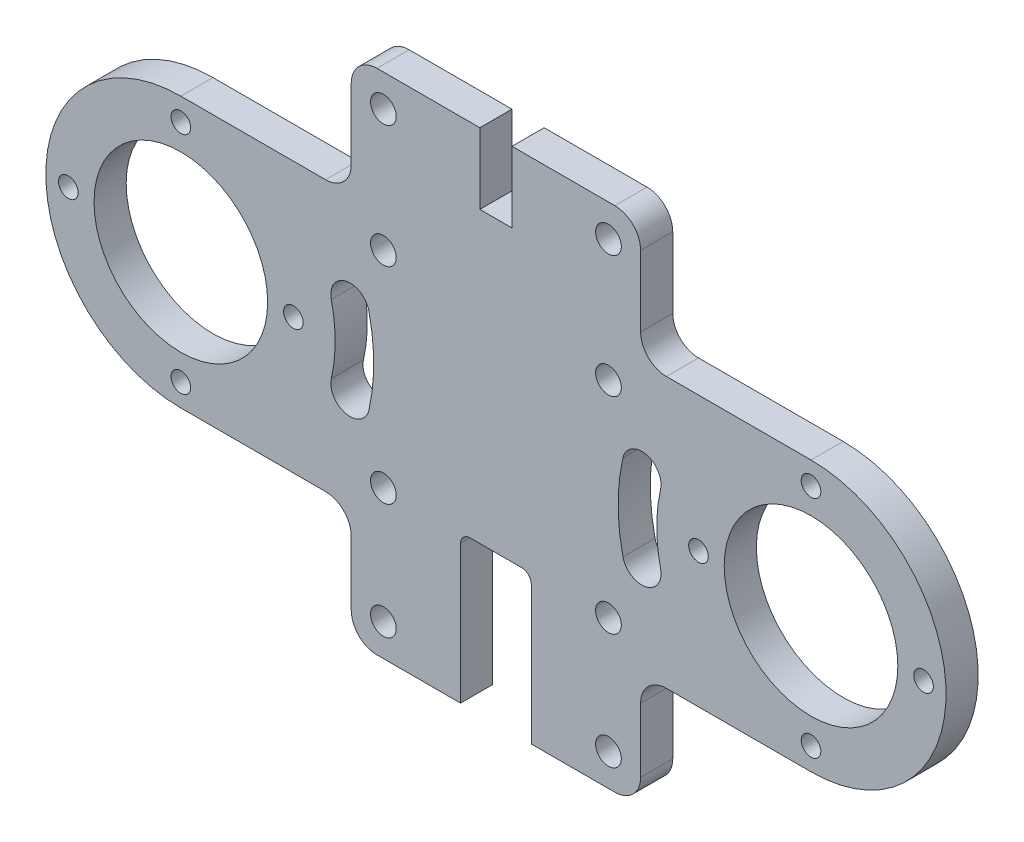
SolidWorks part; units mm, degrees
material "6061 Alloy"
ref_plane "Front Plane" through (0, 0, 0) normal (0, 0, 1) x (1, 0, 0)
ref_plane "Top Plane" through (0, 0, 0) normal (0, 1, 0) x (1, 0, 0)
ref_plane "Right Plane" through (0, 0, 0) normal (1, 0, 0) x (0, 0, -1)
sketch "Sketch1" plane through (0, 0, 0) normal (0, 0, 1) x (1, 0, 0)
  line L0 (-49, 26) -> (49, 26)
  line L1 (-49, -16) -> (49, -16)
  arc A1 (-49, 26) -> (-49, -16) centre (-49, 5) ccw
  arc A3 (49, -16) -> (49, 26) centre (49, 5) ccw
  arc A4 (49, -14) -> (49, -11) centre (49, -12.5) ccw construction
  arc A5 (66.5, 3.5) -> (66.5, 6.5) centre (66.5, 5) ccw construction
  arc A6 (31.5, 3.5) -> (31.5, 6.5) centre (31.5, 5) ccw construction
  arc A7 (49, 21) -> (49, 24) centre (49, 22.5) ccw construction
  arc A8 (-49, -14) -> (-49, -11) centre (-49, -12.5) ccw construction
  arc A9 (-31.5, 3.5) -> (-31.5, 6.5) centre (-31.5, 5) ccw construction
  arc A10 (-66.5, 3.5) -> (-66.5, 6.5) centre (-66.5, 5) ccw construction
  arc A11 (-49, 24) -> (-49, 21) centre (-49, 22.5) ccw construction
  circle A12 centre (49, -12.5) radius 1.5
  circle A13 centre (66.5, 5) radius 1.5
  circle A14 centre (31.5, 5) radius 1.5
  circle A15 centre (49, 22.5) radius 1.5
  circle A16 centre (-49, -12.5) radius 1.5
  circle A17 centre (-31.5, 5) radius 1.5
  circle A18 centre (-66.5, 5) radius 1.5
  circle A19 centre (-49, 22.5) radius 1.5
  arc A20 (-49, -8) -> (-49, 18) centre (-49, 5) ccw construction
  circle A21 centre (-49, 5) radius 13
  arc A22 (49, -8) -> (49, 18) centre (49, 5) ccw construction
  circle A23 centre (49, 5) radius 13
  dimension "D1" = 21
  dimension "D2" = 26
extrude "Boss-Extrude1" add sketch "Sketch1" along normal blind 5
sketch "Sketch2" plane through (0, 0, 0) normal (0, 0, -1) x (-1, 0, 0)
  circle A0 centre (-49, 5) radius 13.5
  circle A1 centre (49, 5) radius 13.5
  circle A2 centre (-49, 5) radius 13 construction
  dimension "D1" = 27
extrude "Cut-Extrude1" cut sketch "Sketch2" against normal blind 10
sketch "Sketch3" plane through (0, 0, 5) normal (0, 0, 1) x (1, 0, 0)
  line L0 (49, 26) -> (-49, 26) construction
  line L1 (0, 26) -> (0, -16) construction
  line L2 (-49, -16) -> (49, -16) construction
  line L3 (0, 5) -> (-11.8321, 5) construction
  circle A0 centre (49, 5) radius 24
  circle A1 centre (49, 5) radius 30
  arc A2 (19.7501, 11.6667) -> (25.6001, 10.3333) centre (22.6751, 11) cw
  arc A3 (19.7501, -1.6667) -> (25.6001, -0.3333) centre (22.6751, -1) ccw
  arc A4 (-19.7501, -1.6667) -> (-25.6001, -0.3333) centre (-22.6751, -1) cw
  arc A5 (-19.7501, 11.6667) -> (-25.6001, 10.3333) centre (-22.6751, 11) ccw
  circle A6 centre (-49, 5) radius 30
  circle A7 centre (-49, 5) radius 24
  dimension "D1" = 48
  dimension "D2" = 60
  dimension "D3" = 15
extrude "Cut-Extrude2" cut sketch "Sketch3" against normal blind 10 contours A5 A7 A4 A6 | A1 A3 A0 A2 region at (22.3515, 5, 5) region at (-22.3515, 5, 5)
sketch "Sketch4" plane through (0, 0, 0) normal (0, 0, -1) x (-1, 0, 0)
  line L0 (49, -16) -> (-49, -16) construction
  line L1 (5.5, -16) -> (-5.5, -16)
  line L2 (5.5, -16) -> (5.5, -11)
  line L3 (5.5, -11) -> (-5.5, -11)
  line L4 (-5.5, -16) -> (-5.5, -11)
  line L5 (0, 26) -> (0, -16) construction
  line L6 (-49, 26) -> (49, 26) construction
  dimension "D1" = 11
  dimension "D2" = 5
extrude "Cut-Extrude3" cut sketch "Sketch4" against normal blind 82
fillet "Fillet1" radius 1.5 2 edges at (-5.5, -11, 2.5) (5.5, -11, 2.5)
sketch "Sketch5" plane through (0, 0, 0) normal (0, 0, -1) x (-1, 0, 0)
  line L0 (0, 26) -> (0, -34) construction
  line L1 (-22.5, 45) -> (22.5, 45)
  line L2 (-22.5, 45) -> (-22.5, -34)
  line L3 (-22.5, -34) -> (22.5, -34)
  line L4 (22.5, 45) -> (22.5, -34)
  line L5 (-49, 26) -> (49, 26) construction
  line L6 (-5.5, -12.5) -> (-5.5, -16) construction
  line L7 (-2.5, 45) -> (2.5, 45)
  line L8 (-2.5, 45) -> (-2.5, 34)
  line L9 (-2.5, 34) -> (2.5, 34)
  line L10 (2.5, 45) -> (2.5, 34)
  line L11 (4, -11) -> (-4, -11) construction
  line L12 (5.5, -16) -> (5.5, -12.5) construction
  line L13 (-5.5, -12.5) -> (-5.5, -34)
  line L14 (4, -11) -> (-4, -11)
  line L15 (5.5, -34) -> (5.5, -12.5)
  line L17 (-17.5, 40) -> (17.5, 40) construction
  line L18 (-17.5, 40) -> (-17.5, -29) construction
  line L19 (-17.5, -29) -> (17.5, -29) construction
  line L20 (17.5, 40) -> (17.5, -29) construction
  arc A0 (-4, -11) -> (-5.5, -12.5) centre (-4, -12.5) ccw construction
  arc A1 (5.5, -12.5) -> (4, -11) centre (4, -12.5) ccw construction
  arc A2 (-4, -11) -> (-5.5, -12.5) centre (-4, -12.5) ccw
  arc A3 (5.5, -12.5) -> (4, -11) centre (4, -12.5) ccw
  circle A4 centre (-17.5, 40) radius 2
  circle A5 centre (17.5, 40) radius 2
  circle A6 centre (-17.5, -29) radius 2
  circle A7 centre (17.5, -29) radius 2
  arc M13 (19.7501, -1.6667) -> (19.7501, 11.6667) centre (49, 5) cw
  arc M14 (19.7501, 11.6667) -> (25.6001, 10.3333) centre (22.6751, 11) cw
  arc M16 (25.6001, -0.3333) -> (19.7501, -1.6667) centre (22.6751, -1) cw
  arc M17 (-25.6001, 10.3333) -> (-19.7501, 11.6667) centre (-22.6751, 11) cw
  arc M18 (-19.7501, 11.6667) -> (-19.7501, -1.6667) centre (-49, 5) cw
  arc M19 (-19.7501, -1.6667) -> (-25.6001, -0.3333) centre (-22.6751, -1) cw
  line M23 (-4, -11) -> (4, -11)
  arc M24 (4, -11) -> (5.5, -12.5) centre (4, -12.5) cw
  line M25 (5.5, -12.5) -> (5.5, -16)
  line M26 (5.5, -16) -> (49, -16)
  line M28 (49, 26) -> (-49, 26)
  line M30 (-49, -16) -> (-5.5, -16)
  line M31 (-5.5, -16) -> (-5.5, -12.5)
  arc M32 (-5.5, -12.5) -> (-4, -11) centre (-4, -12.5) cw
  dimension "D10" = 4
  dimension "D1" = 45
  dimension "D2" = 34
  dimension "D3" = 45
  dimension "D4" = 5
  dimension "D5" = 11
  dimension "D6" = 5
  dimension "D7" = 5
  dimension "D8" = 5
  dimension "D9" = 5
extrude "Boss-Extrude2" add sketch "Sketch5" against normal blind 5 contours L1 L10 L9 L8 L2 L4 A5 A4 M28 | L4 L2 M28 M17 M18 M19 M30 M31 M32 M23 M24 M25 M26 M16 M13 M14 | L13 L2 L3 A6 M30 | L15 L3 L4 A7 M26 region at (12.5, 44.5115, 0) region at (0, 5.5788, 0) region at (13.8501, -24.8287, 0) region at (-13.8501, -24.8287, 0)
fillet "Fillet2" radius 4 8 edges at (-22.5, -34, 2.5) (-22.5, -16, 2.5) (22.5, -34, 2.5) (22.5, -16, 2.5) (22.5, 45, 2.5) (-22.5, 45, 2.5) (-22.5, 26, 2.5) (22.5, 26, 2.5)
sketch "Sketch6" plane through (0, 0, 0) normal (0, 0, -1) x (-1, 0, 0)
  line L0 (-17.5, 40) -> (-17.5, -29) construction
  line L1 (17.5, 40) -> (17.5, -29) construction
  line L2 (-49, 26) -> (-26.5, 26) construction
  line L3 (-17.5, 21) -> (17.5, 21) construction
  line L4 (-17.5, 21) -> (-17.5, -11) construction
  line L5 (-17.5, -11) -> (17.5, -11) construction
  line L6 (17.5, 21) -> (17.5, -11) construction
  line L7 (-26.5, -16) -> (-49, -16) construction
  circle A0 centre (-17.5, 21) radius 2
  circle A1 centre (17.5, 21) radius 2
  circle A2 centre (-17.5, -11) radius 2
  circle A3 centre (17.5, -11) radius 2
  dimension "D3" = 4
  dimension "D1" = 5
  dimension "D2" = 5
extrude "Cut-Extrude4" cut sketch "Sketch6" against normal blind 5
sketch "Sketch7" plane through (0, 0, 5) normal (0, 0, 1) x (1, 0, 0)
  circle A0 centre (-49, 22.5) radius 1.525
  circle A1 centre (-66.5, 5) radius 1.525
  circle A2 centre (-31.5, 5) radius 1.525
  circle A3 centre (-49, -12.5) radius 1.525
  circle A4 centre (49, 22.5) radius 1.525
  circle A5 centre (31.5, 5) radius 1.525
  circle A6 centre (66.5, 5) radius 1.525
  circle A7 centre (49, -12.5) radius 1.525
  dimension "D1" = 3.05
extrude "Cut-Extrude5" cut sketch "Sketch7" against normal blind 10
